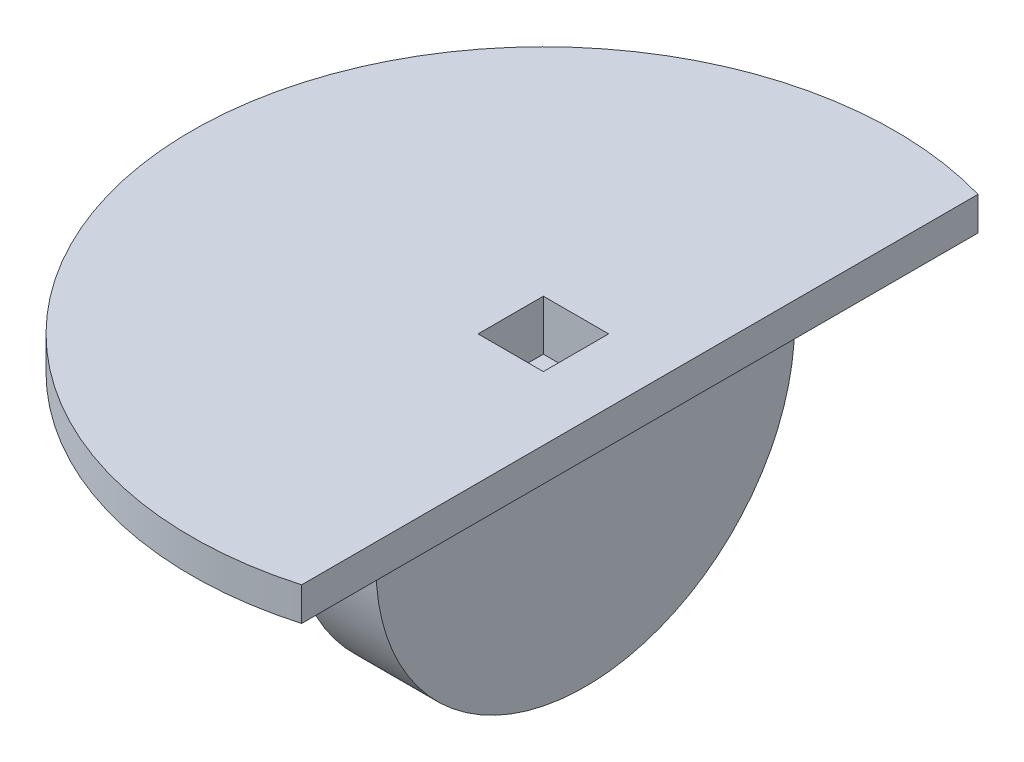
SolidWorks part; units mm, degrees
ref_plane "Front Plane" through (0, 0, 0) normal (0, 0, 1) x (1, 0, 0)
ref_plane "Top Plane" through (0, 0, 0) normal (0, 1, 0) x (1, 0, 0)
ref_plane "Right Plane" through (0, 0, 0) normal (1, 0, 0) x (0, 0, -1)
sketch "Sketch1" plane through (0, 0, 0) normal (0, 1, 0) x (1, 0, 0)
  line L0 (0, 0) -> (5.7604, 0) construction
  line L21 (0, 0) -> (-15, 25.9808) construction
  line L28 (5.7604, 20.1945) -> (5.7604, -20.1945)
  arc A0 (5.7604, 20.1945) -> (5.7604, -20.1945) centre (0, 0) ccw
  point P3 (0, 0)
  point P7 (5.7604, 0)
  point P8 (0, 0)
  point P29 (0, 0)
  dimension "D1" = 42
extrude "Boss-Extrude1" add sketch "Sketch1" along normal blind 2 contours A0 | A0 | A0 | A0 L28 region at (-5.8936, 0, 0)
ref_plane "Plane1" through (0, 2, 0) normal (0, 1, 0) x (1, 0, 0)
sketch "Sketch2" plane through (0, 2, 0) normal (0, 1, 0) x (1, 0, 0)
  line L1 (-1.95, 1.95) -> (1.95, 1.95)
  line L2 (-1.95, 1.95) -> (-1.95, -1.95)
  line L3 (-1.95, -1.95) -> (1.95, -1.95)
  line L4 (1.95, 1.95) -> (1.95, -1.95)
  point P4 (0, -1.95)
  point P6 (-1.95, 0)
  dimension "D1" = 3.9
sketch "Sketch4" plane through (0, 0, 0) normal (0, 1, 0) x (1, 0, 0)
  line L1 (2.5, 12.5) -> (-2.5, 12.5)
  line L2 (2.5, 12.5) -> (2.5, -12.5)
  line L3 (2.5, -12.5) -> (-2.5, -12.5)
  line L4 (-2.5, 12.5) -> (-2.5, -12.5)
  dimension "D1" = 25
  dimension "D2" = 5
  dimension "D3" = 2.5
  dimension "D4" = 12.5
extrude "Boss-Extrude3" add sketch "Sketch4" against normal blind 15
fillet "Fillet1" 2 edges at (0, -15, 12.5) (0, -15, -12.5) type full round first side face at (0, -7.5, 12.5) second side face at (0, -7.5, -12.5) middle face at (0, -15, 0)
extrude "Cut-Extrude1" cut sketch "Sketch2" against normal blind 3
